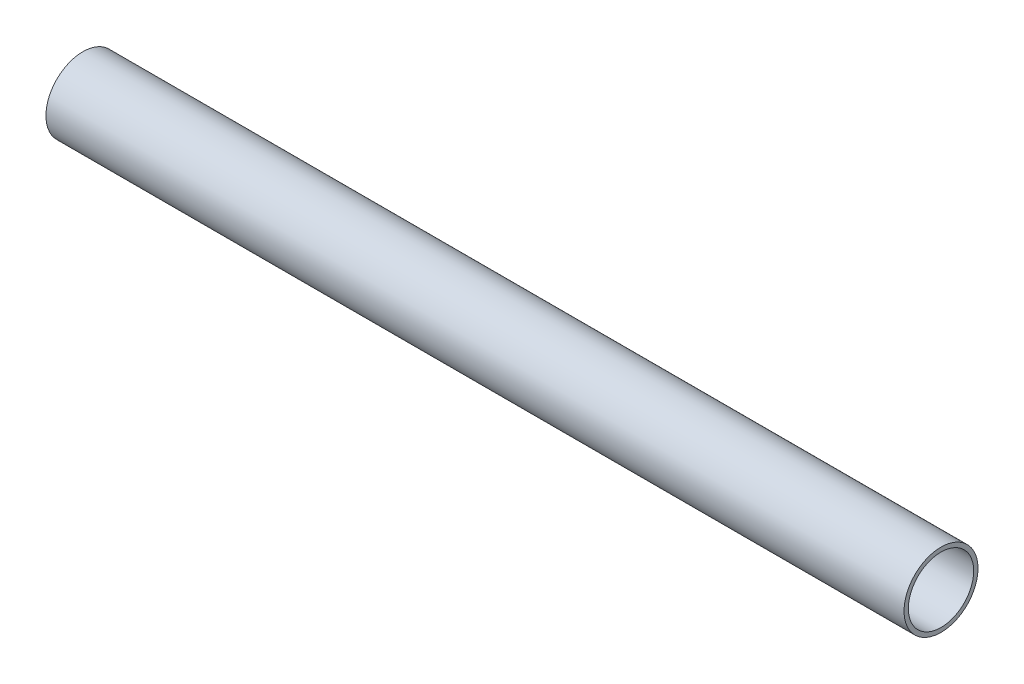
SolidWorks part; units mm, degrees
ref_plane "Alzado" through (0, 0, 0) normal (0, 0, 1) x (1, 0, 0)
ref_plane "Planta" through (0, 0, 0) normal (0, 1, 0) x (1, 0, 0)
ref_plane "Vista lateral" through (0, 0, 0) normal (1, 0, 0) x (0, 0, -1)
sketch "Croquis2" plane through (0, 0, 0) normal (1, 0, 0) x (0, 0, -1)
  circle A0 centre (0, 0) radius 76.2
  circle A1 centre (0, 0) radius 86.2
  dimension "D1" = 152.4
  dimension "D2" = 10
extrude "Saliente-Extruir1" add sketch "Croquis2" along normal blind 2000
